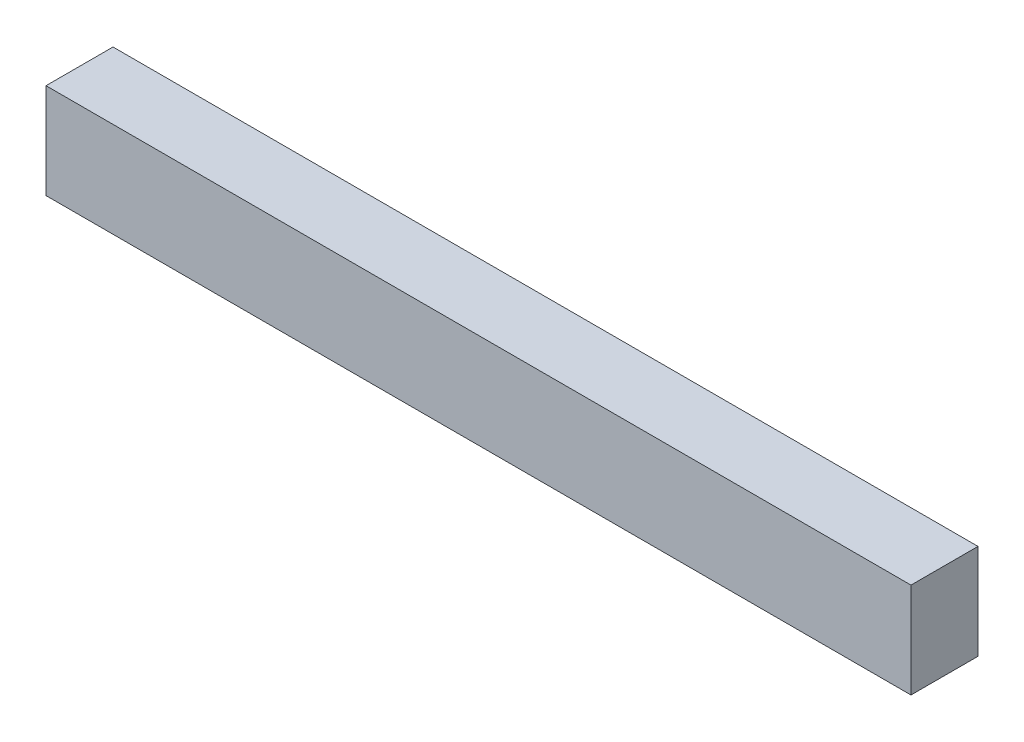
SolidWorks part; units mm, degrees
ref_plane "Front Plane" through (0, 0, 0) normal (0, 0, 1) x (1, 0, 0)
ref_plane "Top Plane" through (0, 0, 0) normal (0, 1, 0) x (1, 0, 0)
ref_plane "Right Plane" through (0, 0, 0) normal (1, 0, 0) x (0, 0, -1)
sketch "Sketch1" plane through (0, 0, 0) normal (0, 1, 0) x (1, 0, 0)
  line L0 (4.04, 3) -> (4.04, 1.5)
  line L1 (0, 0) -> (90.86, 0)
  line L2 (0, 0) -> (0, 7.04)
  line L3 (0, 7.04) -> (90.86, 7.04)
  line L4 (90.86, 0) -> (90.86, 7.04)
  line L5 (1.5, 3) -> (3, 3)
  line L6 (1.5, 3) -> (1.5, 1.5)
  line L7 (1.5, 1.5) -> (3, 1.5)
  line L8 (3, 3) -> (3, 1.5)
  line L9 (4.04, 3) -> (5.54, 3)
  line L10 (5.54, 3) -> (5.54, 1.5)
  line L11 (4.04, 1.5) -> (5.54, 1.5)
  line L12 (6.58, 3) -> (6.58, 1.5)
  line L13 (6.58, 3) -> (8.08, 3)
  line L14 (8.08, 3) -> (8.08, 1.5)
  line L15 (6.58, 1.5) -> (8.08, 1.5)
  line L16 (9.12, 3) -> (9.12, 1.5)
  line L17 (9.12, 3) -> (10.62, 3)
  line L18 (10.62, 3) -> (10.62, 1.5)
  line L19 (9.12, 1.5) -> (10.62, 1.5)
  line L20 (11.66, 3) -> (11.66, 1.5)
  line L21 (11.66, 3) -> (13.16, 3)
  line L22 (13.16, 3) -> (13.16, 1.5)
  line L23 (11.66, 1.5) -> (13.16, 1.5)
  line L24 (14.2, 3) -> (14.2, 1.5)
  line L25 (14.2, 3) -> (15.7, 3)
  line L26 (15.7, 3) -> (15.7, 1.5)
  line L27 (14.2, 1.5) -> (15.7, 1.5)
  line L28 (16.74, 3) -> (16.74, 1.5)
  line L29 (16.74, 3) -> (18.24, 3)
  line L30 (18.24, 3) -> (18.24, 1.5)
  line L31 (16.74, 1.5) -> (18.24, 1.5)
  line L32 (19.28, 3) -> (19.28, 1.5)
  line L33 (19.28, 3) -> (20.78, 3)
  line L34 (20.78, 3) -> (20.78, 1.5)
  line L35 (19.28, 1.5) -> (20.78, 1.5)
  line L36 (21.82, 3) -> (21.82, 1.5)
  line L37 (21.82, 3) -> (23.32, 3)
  line L38 (23.32, 3) -> (23.32, 1.5)
  line L39 (21.82, 1.5) -> (23.32, 1.5)
  line L40 (24.36, 3) -> (24.36, 1.5)
  line L41 (24.36, 3) -> (25.86, 3)
  line L42 (25.86, 3) -> (25.86, 1.5)
  line L43 (24.36, 1.5) -> (25.86, 1.5)
  line L44 (26.9, 3) -> (26.9, 1.5)
  line L45 (26.9, 3) -> (28.4, 3)
  line L46 (28.4, 3) -> (28.4, 1.5)
  line L47 (26.9, 1.5) -> (28.4, 1.5)
  line L48 (29.44, 3) -> (29.44, 1.5)
  line L49 (29.44, 3) -> (30.94, 3)
  line L50 (30.94, 3) -> (30.94, 1.5)
  line L51 (29.44, 1.5) -> (30.94, 1.5)
  line L52 (31.98, 3) -> (31.98, 1.5)
  line L53 (31.98, 3) -> (33.48, 3)
  line L54 (33.48, 3) -> (33.48, 1.5)
  line L55 (31.98, 1.5) -> (33.48, 1.5)
  line L56 (34.52, 3) -> (34.52, 1.5)
  line L57 (34.52, 3) -> (36.02, 3)
  line L58 (36.02, 3) -> (36.02, 1.5)
  line L59 (34.52, 1.5) -> (36.02, 1.5)
  line L60 (37.06, 3) -> (37.06, 1.5)
  line L61 (37.06, 3) -> (38.56, 3)
  line L62 (38.56, 3) -> (38.56, 1.5)
  line L63 (37.06, 1.5) -> (38.56, 1.5)
  line L64 (39.6, 3) -> (39.6, 1.5)
  line L65 (39.6, 3) -> (41.1, 3)
  line L66 (41.1, 3) -> (41.1, 1.5)
  line L67 (39.6, 1.5) -> (41.1, 1.5)
  line L68 (42.14, 3) -> (42.14, 1.5)
  line L69 (42.14, 3) -> (43.64, 3)
  line L70 (43.64, 3) -> (43.64, 1.5)
  line L71 (42.14, 1.5) -> (43.64, 1.5)
  line L72 (44.68, 3) -> (44.68, 1.5)
  line L73 (44.68, 3) -> (46.18, 3)
  line L74 (46.18, 3) -> (46.18, 1.5)
  line L75 (44.68, 1.5) -> (46.18, 1.5)
  line L76 (47.22, 3) -> (47.22, 1.5)
  line L77 (47.22, 3) -> (48.72, 3)
  line L78 (48.72, 3) -> (48.72, 1.5)
  line L79 (47.22, 1.5) -> (48.72, 1.5)
  line L80 (49.76, 3) -> (49.76, 1.5)
  line L81 (49.76, 3) -> (51.26, 3)
  line L82 (51.26, 3) -> (51.26, 1.5)
  line L83 (49.76, 1.5) -> (51.26, 1.5)
  line L84 (52.3, 3) -> (52.3, 1.5)
  line L85 (52.3, 3) -> (53.8, 3)
  line L86 (53.8, 3) -> (53.8, 1.5)
  line L87 (52.3, 1.5) -> (53.8, 1.5)
  line L88 (54.84, 3) -> (54.84, 1.5)
  line L89 (54.84, 3) -> (56.34, 3)
  line L90 (56.34, 3) -> (56.34, 1.5)
  line L91 (54.84, 1.5) -> (56.34, 1.5)
  line L92 (57.38, 3) -> (57.38, 1.5)
  line L93 (57.38, 3) -> (58.88, 3)
  line L94 (58.88, 3) -> (58.88, 1.5)
  line L95 (57.38, 1.5) -> (58.88, 1.5)
  line L96 (59.92, 3) -> (59.92, 1.5)
  line L97 (59.92, 3) -> (61.42, 3)
  line L98 (61.42, 3) -> (61.42, 1.5)
  line L99 (59.92, 1.5) -> (61.42, 1.5)
  line L100 (62.46, 3) -> (62.46, 1.5)
  line L101 (62.46, 3) -> (63.96, 3)
  line L102 (63.96, 3) -> (63.96, 1.5)
  line L103 (62.46, 1.5) -> (63.96, 1.5)
  line L104 (65, 3) -> (65, 1.5)
  line L105 (65, 3) -> (66.5, 3)
  line L106 (66.5, 3) -> (66.5, 1.5)
  line L107 (65, 1.5) -> (66.5, 1.5)
  line L108 (67.54, 3) -> (67.54, 1.5)
  line L109 (67.54, 3) -> (69.04, 3)
  line L110 (69.04, 3) -> (69.04, 1.5)
  line L111 (67.54, 1.5) -> (69.04, 1.5)
  line L112 (70.08, 3) -> (70.08, 1.5)
  line L113 (70.08, 3) -> (71.58, 3)
  line L114 (71.58, 3) -> (71.58, 1.5)
  line L115 (70.08, 1.5) -> (71.58, 1.5)
  line L116 (72.62, 3) -> (72.62, 1.5)
  line L117 (72.62, 3) -> (74.12, 3)
  line L118 (74.12, 3) -> (74.12, 1.5)
  line L119 (72.62, 1.5) -> (74.12, 1.5)
  line L120 (75.16, 3) -> (75.16, 1.5)
  line L121 (75.16, 3) -> (76.66, 3)
  line L122 (76.66, 3) -> (76.66, 1.5)
  line L123 (75.16, 1.5) -> (76.66, 1.5)
  line L124 (77.7, 3) -> (77.7, 1.5)
  line L125 (77.7, 3) -> (79.2, 3)
  line L126 (79.2, 3) -> (79.2, 1.5)
  line L127 (77.7, 1.5) -> (79.2, 1.5)
  line L128 (80.24, 3) -> (80.24, 1.5)
  line L129 (80.24, 3) -> (81.74, 3)
  line L130 (81.74, 3) -> (81.74, 1.5)
  line L131 (80.24, 1.5) -> (81.74, 1.5)
  line L132 (82.78, 3) -> (82.78, 1.5)
  line L133 (82.78, 3) -> (84.28, 3)
  line L134 (84.28, 3) -> (84.28, 1.5)
  line L135 (82.78, 1.5) -> (84.28, 1.5)
  line L136 (85.32, 3) -> (85.32, 1.5)
  line L137 (85.32, 3) -> (86.82, 3)
  line L138 (86.82, 3) -> (86.82, 1.5)
  line L139 (85.32, 1.5) -> (86.82, 1.5)
  line L140 (87.86, 3) -> (87.86, 1.5)
  line L141 (87.86, 3) -> (89.36, 3)
  line L142 (89.36, 3) -> (89.36, 1.5)
  line L143 (87.86, 1.5) -> (89.36, 1.5)
  line L144 (4.04, 5.54) -> (4.04, 4.04)
  line L145 (4.04, 5.54) -> (5.54, 5.54)
  line L146 (5.54, 5.54) -> (5.54, 4.04)
  line L147 (4.04, 4.04) -> (5.54, 4.04)
  line L148 (6.58, 5.54) -> (6.58, 4.04)
  line L149 (6.58, 5.54) -> (8.08, 5.54)
  line L150 (8.08, 5.54) -> (8.08, 4.04)
  line L151 (6.58, 4.04) -> (8.08, 4.04)
  line L152 (9.12, 5.54) -> (9.12, 4.04)
  line L153 (9.12, 5.54) -> (10.62, 5.54)
  line L154 (10.62, 5.54) -> (10.62, 4.04)
  line L155 (9.12, 4.04) -> (10.62, 4.04)
  line L156 (11.66, 5.54) -> (11.66, 4.04)
  line L157 (11.66, 5.54) -> (13.16, 5.54)
  line L158 (13.16, 5.54) -> (13.16, 4.04)
  line L159 (11.66, 4.04) -> (13.16, 4.04)
  line L160 (14.2, 5.54) -> (14.2, 4.04)
  line L161 (14.2, 5.54) -> (15.7, 5.54)
  line L162 (15.7, 5.54) -> (15.7, 4.04)
  line L163 (14.2, 4.04) -> (15.7, 4.04)
  line L164 (16.74, 5.54) -> (16.74, 4.04)
  line L165 (16.74, 5.54) -> (18.24, 5.54)
  line L166 (18.24, 5.54) -> (18.24, 4.04)
  line L167 (16.74, 4.04) -> (18.24, 4.04)
  line L168 (19.28, 5.54) -> (19.28, 4.04)
  line L169 (19.28, 5.54) -> (20.78, 5.54)
  line L170 (20.78, 5.54) -> (20.78, 4.04)
  line L171 (19.28, 4.04) -> (20.78, 4.04)
  line L172 (21.82, 5.54) -> (21.82, 4.04)
  line L173 (21.82, 5.54) -> (23.32, 5.54)
  line L174 (23.32, 5.54) -> (23.32, 4.04)
  line L175 (21.82, 4.04) -> (23.32, 4.04)
  line L176 (24.36, 5.54) -> (24.36, 4.04)
  line L177 (24.36, 5.54) -> (25.86, 5.54)
  line L178 (25.86, 5.54) -> (25.86, 4.04)
  line L179 (24.36, 4.04) -> (25.86, 4.04)
  line L180 (26.9, 5.54) -> (26.9, 4.04)
  line L181 (26.9, 5.54) -> (28.4, 5.54)
  line L182 (28.4, 5.54) -> (28.4, 4.04)
  line L183 (26.9, 4.04) -> (28.4, 4.04)
  line L184 (29.44, 5.54) -> (29.44, 4.04)
  line L185 (29.44, 5.54) -> (30.94, 5.54)
  line L186 (30.94, 5.54) -> (30.94, 4.04)
  line L187 (29.44, 4.04) -> (30.94, 4.04)
  line L188 (31.98, 5.54) -> (31.98, 4.04)
  line L189 (31.98, 5.54) -> (33.48, 5.54)
  line L190 (33.48, 5.54) -> (33.48, 4.04)
  line L191 (31.98, 4.04) -> (33.48, 4.04)
  line L192 (34.52, 5.54) -> (34.52, 4.04)
  line L193 (34.52, 5.54) -> (36.02, 5.54)
  line L194 (36.02, 5.54) -> (36.02, 4.04)
  line L195 (34.52, 4.04) -> (36.02, 4.04)
  line L196 (37.06, 5.54) -> (37.06, 4.04)
  line L197 (37.06, 5.54) -> (38.56, 5.54)
  line L198 (38.56, 5.54) -> (38.56, 4.04)
  line L199 (37.06, 4.04) -> (38.56, 4.04)
  line L200 (39.6, 5.54) -> (39.6, 4.04)
  line L201 (39.6, 5.54) -> (41.1, 5.54)
  line L202 (41.1, 5.54) -> (41.1, 4.04)
  line L203 (39.6, 4.04) -> (41.1, 4.04)
  line L204 (42.14, 5.54) -> (42.14, 4.04)
  line L205 (42.14, 5.54) -> (43.64, 5.54)
  line L206 (43.64, 5.54) -> (43.64, 4.04)
  line L207 (42.14, 4.04) -> (43.64, 4.04)
  line L208 (44.68, 5.54) -> (44.68, 4.04)
  line L209 (44.68, 5.54) -> (46.18, 5.54)
  line L210 (46.18, 5.54) -> (46.18, 4.04)
  line L211 (44.68, 4.04) -> (46.18, 4.04)
  line L212 (47.22, 5.54) -> (47.22, 4.04)
  line L213 (47.22, 5.54) -> (48.72, 5.54)
  line L214 (48.72, 5.54) -> (48.72, 4.04)
  line L215 (47.22, 4.04) -> (48.72, 4.04)
  line L216 (49.76, 5.54) -> (49.76, 4.04)
  line L217 (49.76, 5.54) -> (51.26, 5.54)
  line L218 (51.26, 5.54) -> (51.26, 4.04)
  line L219 (49.76, 4.04) -> (51.26, 4.04)
  line L220 (52.3, 5.54) -> (52.3, 4.04)
  line L221 (52.3, 5.54) -> (53.8, 5.54)
  line L222 (53.8, 5.54) -> (53.8, 4.04)
  line L223 (52.3, 4.04) -> (53.8, 4.04)
  line L224 (54.84, 5.54) -> (54.84, 4.04)
  line L225 (54.84, 5.54) -> (56.34, 5.54)
  line L226 (56.34, 5.54) -> (56.34, 4.04)
  line L227 (54.84, 4.04) -> (56.34, 4.04)
  line L228 (57.38, 5.54) -> (57.38, 4.04)
  line L229 (57.38, 5.54) -> (58.88, 5.54)
  line L230 (58.88, 5.54) -> (58.88, 4.04)
  line L231 (57.38, 4.04) -> (58.88, 4.04)
  line L232 (59.92, 5.54) -> (59.92, 4.04)
  line L233 (59.92, 5.54) -> (61.42, 5.54)
  line L234 (61.42, 5.54) -> (61.42, 4.04)
  line L235 (59.92, 4.04) -> (61.42, 4.04)
  line L236 (62.46, 5.54) -> (62.46, 4.04)
  line L237 (62.46, 5.54) -> (63.96, 5.54)
  line L238 (63.96, 5.54) -> (63.96, 4.04)
  line L239 (62.46, 4.04) -> (63.96, 4.04)
  line L240 (65, 5.54) -> (65, 4.04)
  line L241 (65, 5.54) -> (66.5, 5.54)
  line L242 (66.5, 5.54) -> (66.5, 4.04)
  line L243 (65, 4.04) -> (66.5, 4.04)
  line L244 (67.54, 5.54) -> (67.54, 4.04)
  line L245 (67.54, 5.54) -> (69.04, 5.54)
  line L246 (69.04, 5.54) -> (69.04, 4.04)
  line L247 (67.54, 4.04) -> (69.04, 4.04)
  line L248 (70.08, 5.54) -> (70.08, 4.04)
  line L249 (70.08, 5.54) -> (71.58, 5.54)
  line L250 (71.58, 5.54) -> (71.58, 4.04)
  line L251 (70.08, 4.04) -> (71.58, 4.04)
  line L252 (72.62, 5.54) -> (72.62, 4.04)
  line L253 (72.62, 5.54) -> (74.12, 5.54)
  line L254 (74.12, 5.54) -> (74.12, 4.04)
  line L255 (72.62, 4.04) -> (74.12, 4.04)
  line L256 (75.16, 5.54) -> (75.16, 4.04)
  line L257 (75.16, 5.54) -> (76.66, 5.54)
  line L258 (76.66, 5.54) -> (76.66, 4.04)
  line L259 (75.16, 4.04) -> (76.66, 4.04)
  line L260 (77.7, 5.54) -> (77.7, 4.04)
  line L261 (77.7, 5.54) -> (79.2, 5.54)
  line L262 (79.2, 5.54) -> (79.2, 4.04)
  line L263 (77.7, 4.04) -> (79.2, 4.04)
  line L264 (80.24, 5.54) -> (80.24, 4.04)
  line L265 (80.24, 5.54) -> (81.74, 5.54)
  line L266 (81.74, 5.54) -> (81.74, 4.04)
  line L267 (80.24, 4.04) -> (81.74, 4.04)
  line L268 (82.78, 5.54) -> (82.78, 4.04)
  line L269 (82.78, 5.54) -> (84.28, 5.54)
  line L270 (84.28, 5.54) -> (84.28, 4.04)
  line L271 (82.78, 4.04) -> (84.28, 4.04)
  line L272 (85.32, 5.54) -> (85.32, 4.04)
  line L273 (85.32, 5.54) -> (86.82, 5.54)
  line L274 (86.82, 5.54) -> (86.82, 4.04)
  line L275 (85.32, 4.04) -> (86.82, 4.04)
  line L276 (87.86, 5.54) -> (87.86, 4.04)
  line L277 (87.86, 5.54) -> (89.36, 5.54)
  line L278 (89.36, 5.54) -> (89.36, 4.04)
  line L279 (87.86, 4.04) -> (89.36, 4.04)
  line L280 (1.5, 5.54) -> (1.5, 4.04)
  line L281 (1.5, 5.54) -> (3, 5.54)
  line L282 (3, 5.54) -> (3, 4.04)
  line L283 (1.5, 4.04) -> (3, 4.04)
  dimension "D1" = 1.5
  dimension "D2" = 1.5
  dimension "D3" = 1.5
  dimension "D6" = 7.04
  dimension "D7" = 1.5
  dimension "D8" = 90.86
  dimension "D9" = 1.04
  dimension "D10" = 1.04
  dimension "D4" = 35
  dimension "D5" = 2
extrude "Boss-Extrude1" add sketch "Sketch1" along normal blind 8
sketch "Sketch2" plane through (0, 8, 0) normal (0, 1, 0) x (1, 0, 0)
  line L1 (0, 7.04) -> (90.86, 7.04)
  line L2 (0, 7.04) -> (0, 0)
  line L3 (0, 0) -> (90.86, 0)
  line L4 (90.86, 7.04) -> (90.86, 0)
extrude "Boss-Extrude2" add sketch "Sketch2" along normal blind 2
